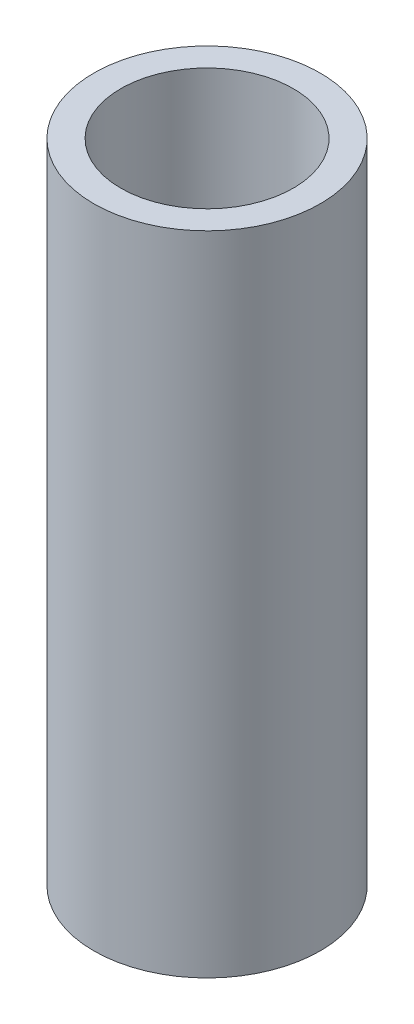
SolidWorks part; units mm, degrees
ref_plane "Front Plane" through (0, 0, 0) normal (0, 0, 1) x (1, 0, 0)
ref_plane "Top Plane" through (0, 0, 0) normal (0, 1, 0) x (1, 0, 0)
ref_plane "Right Plane" through (0, 0, 0) normal (1, 0, 0) x (0, 0, -1)
sketch "Sketch1" plane through (0, 0, 0) normal (0, 1, 0) x (1, 0, 0)
  circle A0 centre (0, 0) radius 1.05
  circle A1 centre (0, 0) radius 0.8
  dimension "D1" = 2.1
  dimension "D2" = 1.6
extrude "Boss-Extrude1" add sketch "Sketch1" along normal blind 6 contours A1 | A0
